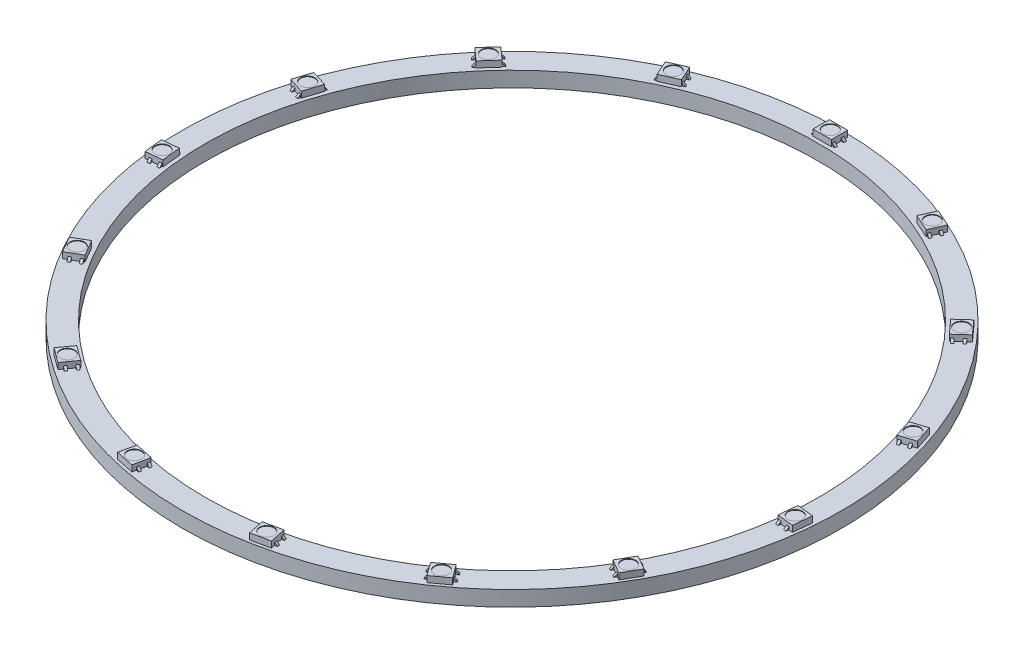
SolidWorks part; units mm, degrees
ref_plane "Ön Düzlem" through (0, 0, 0) normal (0, 0, 1) x (1, 0, 0)
ref_plane "Üst Düzlem" through (0, 0, 0) normal (0, 1, 0) x (1, 0, 0)
ref_plane "Sağ Düzlem" through (0, 0, 0) normal (1, 0, 0) x (0, 0, -1)
sketch "Çizim2" plane through (0, 0, 0) normal (0, 1, 0) x (1, 0, 0)
  circle A0 centre (24.7028, 0) radius 107.5
  circle A1 centre (24.7028, 0) radius 100
  dimension "D1" = 215
  dimension "D2" = 200
extrude "Yükseklik-Ekstrüzyon1" add sketch "Çizim2" along normal blind 5
sketch "Çizim3" plane through (0, 5, 0) normal (0, 1, 0) x (1, 0, 0)
  line L1 (21.7067, 101.1659) -> (27.7067, 101.1659)
  line L2 (21.7067, 101.1659) -> (21.7067, 106.5017)
  line L3 (21.7067, 106.5017) -> (27.7067, 106.5017)
  line L4 (27.7067, 101.1659) -> (27.7067, 106.5017)
  line L5 (21.7067, 101.1659) -> (27.7067, 106.5017) construction
  line L6 (21.7067, 106.5017) -> (27.7067, 101.1659) construction
  point P0 (24.7067, 103.8338)
  dimension "D1" = 6
extrude "Yükseklik-Ekstrüzyon2" add sketch "Çizim3" along normal blind 2
sketch "Çizim4" plane through (0, 5, 0) normal (0, 1, 0) x (1, 0, 0)
  line L0 (21.7067, 106.5017) -> (21.7067, 101.1659) construction
  line L1 (21.7067, 105.2149) -> (20.8067, 105.2149)
  line L2 (21.7067, 105.2149) -> (21.7067, 104.3703)
  line L3 (21.7067, 104.3703) -> (20.8067, 104.3703)
  line L4 (20.8067, 105.2149) -> (20.8067, 104.3703)
  line L6 (28.5989, 105.2149) -> (28.5989, 104.3703)
  line L7 (27.6989, 104.3703) -> (28.5989, 104.3703)
  line L8 (27.6989, 105.2149) -> (27.6989, 104.3703)
  line L9 (27.6989, 105.2149) -> (28.5989, 105.2149)
  line L11 (28.5989, 101.4526) -> (28.5989, 102.2972)
  line L12 (27.6989, 102.2972) -> (28.5989, 102.2972)
  line L13 (27.6989, 101.4526) -> (28.5989, 101.4526)
  line L14 (27.6989, 101.4526) -> (27.6989, 102.2972)
  line L15 (21.7067, 101.4526) -> (21.7067, 102.2972)
  line L16 (21.7067, 102.2972) -> (20.8067, 102.2972)
  line L17 (21.7067, 101.4526) -> (20.8067, 101.4526)
  line L18 (20.8067, 101.4526) -> (20.8067, 102.2972)
  dimension "D1" = 0.9
extrude "Yükseklik-Ekstrüzyon3" add sketch "Çizim4" along normal blind 0.9
chamfer "Pah1" distance 0.9 angle 45 4 edges at (20.8067, 5.9, -104.7926) (28.5989, 5.9, -104.7926) (28.5989, 5.9, -101.8749) (20.8067, 5.9, -101.8749)
sketch "Çizim6" plane through (0, 7, 0) normal (0, 1, 0) x (1, 0, 0)
  circle A0 centre (24.7067, 103.8338) radius 2.3364
extrude "Kes-Ekstrüzyon2" cut sketch "Çizim6" against normal blind 0.2
pattern_circular "Dairesel Kaplama1" count 15 over 360 about axis through (24.7028, 5, 0) along (0, 1, 0) of face at (24.7067, 6.8, -101.4974) of face at (24.7067, 7, -101.4974) of face at (24.7067, 6.8, -101.4974) of face at (21.2567, 5.45, -104.7926) of face at (21.7067, 5.6333, -103.5004) of face at (21.4067, 5.3, -105.2149) of face at (24.7067, 6, -106.5017) of face at (21.4067, 5.3, -104.3703) of face at (21.4067, 5.3, -101.4526) of face at (21.2567, 5.45, -101.8749) of face at (21.4067, 5.3, -102.2972) of face at (28.1528, 5.4461, -101.8749) of face at (27.7067, 5.6308, -103.5004) of face at (28.1528, 5.4461, -104.7926) of face at (28.0041, 5.2974, -105.2149) of face at (28.0041, 5.2974, -101.4526) of face at (28.0041, 5.2974, -104.3703) of face at (28.0041, 5.2974, -102.2972) of face at (24.7067, 6, -101.1659)
